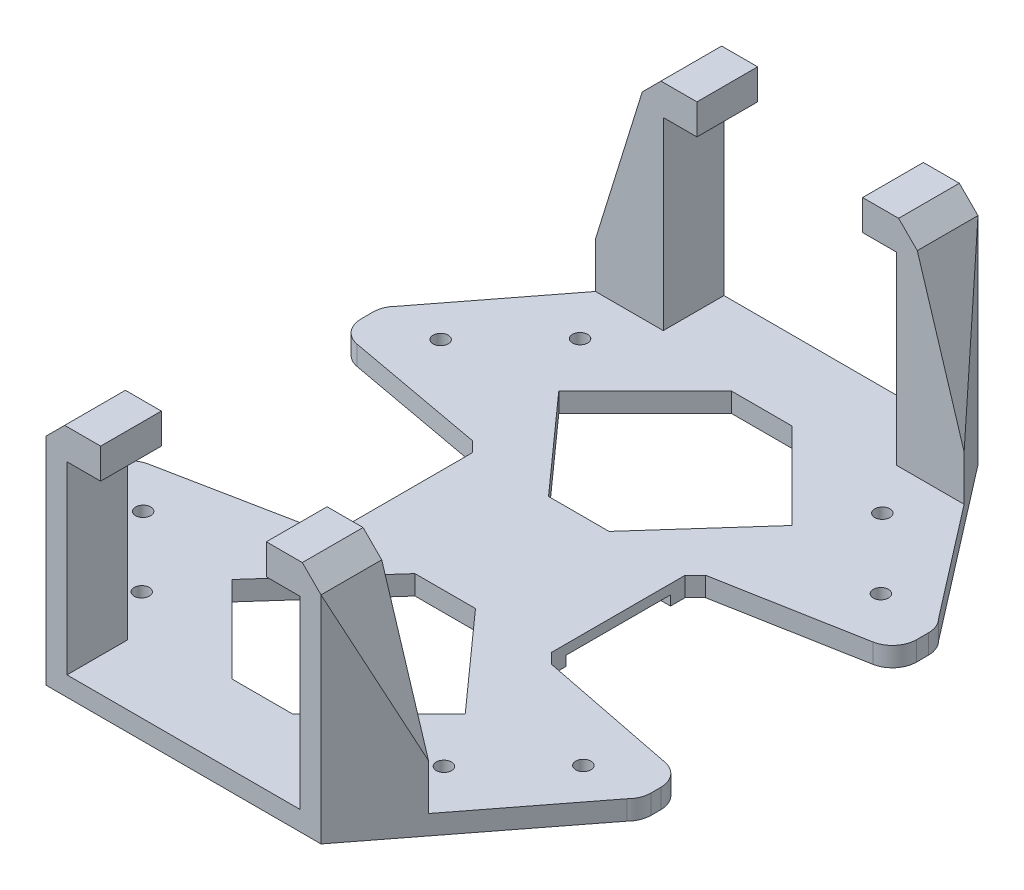
SolidWorks part; units mm, degrees
ref_plane "Front Plane" through (0, 0, 0) normal (0, 0, 1) x (1, 0, 0)
ref_plane "Top Plane" through (0, 0, 0) normal (0, 1, 0) x (1, 0, 0)
ref_plane "Right Plane" through (0, 0, 0) normal (1, 0, 0) x (0, 0, -1)
sketch "Sketch1" plane through (0, 0, 0) normal (0, 1, 0) x (1, 0, 0)
  line L0 (9.3853, 59.817) -> (7.239, 61.9633)
  line L33 (7.239, 114.554) -> (2.8509, 114.554)
  line L34 (7.239, 114.554) -> (7.239, 98.044)
  line L35 (7.239, 98.044) -> (2.8509, 98.044)
  line L36 (2.8509, 114.554) -> (2.8509, 98.044)
  line L37 (7.239, 61.9633) -> (7.239, 98.044)
  line L38 (55.9816, 98.044) -> (60.3697, 98.044)
  line L39 (60.3697, 114.554) -> (60.3697, 98.044)
  line L40 (55.9816, 114.554) -> (60.3697, 114.554)
  line L41 (55.9816, 114.554) -> (55.9816, 98.044)
  line L42 (55.9816, -22.86) -> (55.9816, -6.35)
  line L43 (55.9816, -22.86) -> (60.3697, -22.86)
  line L44 (60.3697, -22.86) -> (60.3697, -6.35)
  line L45 (55.9816, -6.35) -> (60.3697, -6.35)
  line L46 (7.239, -6.35) -> (2.8509, -6.35)
  line L47 (2.8509, -22.86) -> (2.8509, -6.35)
  line L48 (7.239, -22.86) -> (2.8509, -22.86)
  line L49 (7.239, -22.86) -> (7.239, -6.35)
  line L50 (-26.4861, 76.962) -> (2.8509, 106.299)
  line L51 (2.8509, -14.605) -> (-26.4861, 14.732)
  line L52 (-26.4861, 14.732) -> (-26.4861, 76.962)
  line L53 (7.239, 61.9633) -> (-26.4861, 68.1505)
  line L54 (7.239, 29.7307) -> (-26.4861, 23.0392)
  line L55 (60.3697, -14.605) -> (89.7067, 14.732)
  line L56 (9.3853, 31.877) -> (7.239, 29.7307)
  line L57 (9.3853, 59.817) -> (53.8353, 59.817)
  line L58 (9.3853, 59.817) -> (9.3853, 31.877)
  line L59 (9.3853, 31.877) -> (53.8353, 31.877)
  line L60 (53.8353, 59.817) -> (53.8353, 31.877)
  line L61 (7.239, 29.7307) -> (7.239, -6.35)
  line L62 (55.9816, 29.7307) -> (89.7067, 23.0392)
  line L63 (55.9816, 29.7307) -> (55.9816, -6.35)
  line L64 (53.8353, 31.877) -> (55.9816, 29.7307)
  line L65 (53.8353, 59.817) -> (55.9816, 61.9633)
  line L66 (55.9816, 61.9633) -> (55.9816, 98.044)
  line L67 (7.239, 11.6903) -> (25.2794, -6.35)
  line L68 (7.239, 114.554) -> (55.9816, 114.554)
  line L69 (7.239, 114.554) -> (7.239, 98.044)
  line L70 (7.239, 98.044) -> (55.9816, 98.044)
  line L71 (55.9816, 114.554) -> (55.9816, 98.044)
  line L72 (7.239, -6.35) -> (55.9816, -6.35)
  line L73 (7.239, -6.35) -> (7.239, -22.86)
  line L74 (7.239, -22.86) -> (55.9816, -22.86)
  line L75 (55.9816, -6.35) -> (55.9816, -22.86)
  line L76 (55.9816, 11.6903) -> (37.9412, -6.35)
  line L77 (55.9816, 61.9633) -> (89.7067, 68.1505)
  line L78 (7.239, 80.0037) -> (25.2794, 98.044)
  line L79 (55.9816, 80.0037) -> (37.9412, 98.044)
  line L80 (89.7067, 14.732) -> (89.7067, 76.962)
  line L81 (89.7067, 76.962) -> (60.3697, 106.299)
  line L82 (7.239, 80.0037) -> (25.2794, 59.817)
  line L83 (55.9816, 80.0037) -> (37.9412, 59.817)
  line L84 (7.239, 11.6903) -> (25.2794, 31.877)
  line L85 (55.9816, 11.6903) -> (37.9412, 31.877)
  line L86 (31.6103, 114.554) -> (31.6103, 103.0092)
  circle A6 centre (0, 91.694) radius 1.5875
  circle A7 centre (-14.4272, 76.962) radius 1.5875
  circle A8 centre (-14.4272, 14.732) radius 1.5875
  circle A9 centre (0, 0) radius 1.5875
  circle A10 centre (63.2206, 0) radius 1.5875
  circle A11 centre (77.6478, 14.732) radius 1.5875
  circle A12 centre (77.6478, 76.962) radius 1.5875
  circle A13 centre (63.2206, 91.694) radius 1.5875
  dimension "D5" = 44.45
  dimension "D6" = 27.94
extrude "Boss-Extrude2" add sketch "Sketch1" along normal blind 4.064 contours L53 L37 L35 L36 L50 L52 A7 A6 | L61 L54 L52 L51 L47 L46 A9 A8 | L55 L80 L62 L63 L45 L44 A11 A10 | L80 L81 L39 L38 L66 L77 A13 A12 | L34 L70 L41 L68 | L40 L41 L38 L39 | L33 L36 L35 L34 | L48 L49 L46 L47 | L49 L74 L42 L72 | L45 L42 L43 L44 | L63 L76 L72 | L85 L63 L64 L59 | L61 L84 L59 L56 | L61 L72 L67 | L60 L57 L58 L59 | L82 L37 L0 L57 | L37 L78 L70 | L79 L66 L70 | L66 L83 L57 L65 region at (13.3203, 0, -66.6229) region at (31.6103, 0, -45.847) region at (-6.2497, 0, -79.8491) region at (13.3203, 0, -25.0711) region at (13.2525, 0, -92.0306) region at (49.9003, 0, -66.6229) region at (-6.1647, 0, -11.7165) region at (5.0449, 0, -106.299) region at (7.7536, 0, -106.299) region at (69.4703, 0, -79.8491) region at (49.9681, 0, -92.0306) region at (13.2525, 0, 0.3366) region at (49.9003, 0, -25.0711) region at (58.1757, 0, -106.299) region at (5.0449, 0, 14.605) region at (31.6103, 0, 14.605) region at (69.3853, 0, -11.7165) region at (49.9681, 0, 0.3366) region at (58.1757, 0, 14.605)
sketch "Sketch3" plane through (9.3853, 0, 0) normal (-1, 0, 0) x (0, 0, 1)
  line L0 (-59.817, 0) -> (-31.877, 0) construction
  line L13 (-34.9187, 0) -> (-56.7753, 0)
  line L14 (-45.847, 0) -> (-45.847, 2.032)
  line L15 (-34.9187, 2.032) -> (-56.7753, 2.032)
  line L16 (-56.7753, 0) -> (-56.7753, 2.032)
  line L17 (-34.9187, 0) -> (-34.9187, 2.032)
extrude "Boss-Extrude3" add sketch "Sketch1<7>" along normal blind 42.672 contours L33 L36 L35 L34 | L40 L41 L38 L39 | L45 L42 L43 L44 | L48 L49 L46 L47 region at (5.0449, 0, -106.299) region at (58.1757, 0, -106.299) region at (5.0449, 0, 14.605) region at (58.1757, 0, 14.605)
sketch "Sketch1<7>" plane through (0, 0, 0) normal (0, 1, 0) x (1, 0, 0) same geometry as "Sketch1"
fillet "Fillet1" radius 5.08 1 edges at (-26.4861, 2.032, -76.962)
fillet "Fillet2" radius 5.08 1 edges at (-26.4861, 2.032, -68.1505)
fillet "Fillet3" radius 5.08 6 edges at (89.7067, 2.032, -68.1505) (89.7067, 2.032, -76.962) (89.7067, 2.032, -14.732) (89.7067, 2.032, -23.0392) (-26.4861, 2.032, -14.732) (-26.4861, 2.032, -23.0392)
extrude "Cut-Extrude1" cut sketch "Sketch3" against normal through all contours L15 L16 L13 L17
sketch "Sketch4" plane through (0, 0, 0) normal (0, -1, 0) x (1, 0, 0)
  line L0 (60.3697, -114.554) -> (88.2188, -78.4499)
  line L1 (88.2188, -78.4499) -> (60.3697, -106.299)
  line L2 (60.3697, -106.299) -> (60.3697, -114.554)
  line L3 (9.3853, -45.847) -> (28.8242, -45.847)
  line L4 (9.3853, -34.9187) -> (9.3853, -56.7753) construction
  line L5 (31.6103, -34.9187) -> (31.6103, -47.4802)
  line L6 (9.3853, -34.9187) -> (53.8353, -34.9187) construction
  line L7 (-24.9982, -78.4499) -> (2.8509, -106.299)
  line L8 (2.8509, -114.554) -> (-24.9982, -78.4499)
  line L9 (2.8509, -106.299) -> (2.8509, -114.554)
  line L10 (2.8509, 22.86) -> (-24.9982, -13.2441)
  line L11 (2.8509, 14.605) -> (2.8509, 22.86)
  line L12 (-24.9982, -13.2441) -> (2.8509, 14.605)
  line L13 (88.2188, -13.2441) -> (60.3697, 14.605)
  line L14 (60.3697, 22.86) -> (88.2188, -13.2441)
  line L15 (60.3697, 14.605) -> (60.3697, 22.86)
  line M18 (-24.9982, -78.4499) -> (2.8509, -106.299)
  line M19 (2.8509, -106.299) -> (2.8509, -114.554)
  line M21 (60.3697, -114.554) -> (60.3697, -106.299)
  line M22 (60.3697, -106.299) -> (88.2188, -78.4499)
extrude "Boss-Extrude4" add sketch "Sketch4" against normal up to surface (4.064 mm away) contours L8 M19 M18 | L0 M21 M22 | L15 L13 L14 | L10 L12 L11 region at (69.6528, 0, -99.7676) region at (-6.4322, 0, -99.7676) region at (-6.4322, 0, 8.0736) region at (69.6528, 0, 8.0736) up to face at (31.6103, 4.064, -12.4058)
sketch "Sketch6" plane through (0, 42.672, 0) normal (0, 1, 0) x (1, 0, 0)
  line L0 (60.3697, 114.554) -> (60.3697, 101.854)
  line L1 (60.3697, 114.554) -> (60.3697, 98.044) construction
  line L2 (2.8509, -22.86) -> (2.8509, -6.35) construction
  line L3 (60.3697, 101.854) -> (2.8509, 101.854)
  line L4 (60.3697, 101.854) -> (60.3697, -10.16)
  line L5 (60.3697, -10.16) -> (2.8509, -10.16)
  line L6 (2.8509, 101.854) -> (2.8509, -10.16)
  line L7 (55.9816, -22.86) -> (7.239, -22.86) construction
  line M4 (55.9816, 114.554) -> (55.9816, 98.044)
  line M5 (55.9816, 98.044) -> (60.3697, 98.044)
  line M6 (60.3697, 98.044) -> (60.3697, 114.554)
  dimension "D1" = 12.7
  dimension "D2" = 12.7
extrude "Cut-Extrude2" cut sketch "Sketch6" along direction (0, 1, 0) on the side against the normal up to surface (38.608 mm away) contours L3 L6 L5 L4 M5 M4 | L3 M6 M4 M5 region at (58.1757, 42.672, -99.949) region at (31.5412, 42.672, -45.7062) up to face at (31.6103, 4.064, -12.4058)
ref_plane "Plane2" through (0, 0, -45.847) normal (0, 0, 1) x (1, 0, 0)
sketch "Sketch7" plane through (0, 0, 22.86) normal (0, 0, 1) x (1, 0, 0)
  line L1 (60.3697, 42.672) -> (48.9397, 42.672)
  line L2 (60.3697, 42.672) -> (60.3697, 49.022)
  line L3 (60.3697, 49.022) -> (48.9397, 49.022)
  line L4 (48.9397, 42.672) -> (48.9397, 49.022)
  line L5 (2.8509, 42.672) -> (14.2809, 42.672)
  line L6 (2.8509, 42.672) -> (2.8509, 49.022)
  line L7 (2.8509, 49.022) -> (14.2809, 49.022)
  line L8 (14.2809, 42.672) -> (14.2809, 49.022)
  dimension "D1" = 11.43
  dimension "D2" = 11.43
  dimension "D3" = 6.35
  dimension "D4" = 6.35
extrude "Boss-Extrude5" add sketch "Sketch7" against normal up to surface (12.7 mm away) up to face at (58.1757, 23.368, 10.16)
chamfer "Chamfer2" distance 3.904 angle 45 2 edges at (2.8509, 49.022, 16.51) (60.3697, 49.022, 16.51)
sketch "Sketch8" plane through (0, 0, -114.554) normal (0, 0, -1) x (-1, 0, 0)
  line L1 (-60.3697, 42.672) -> (-48.9397, 42.672)
  line L2 (-60.3697, 42.672) -> (-60.3697, 49.022)
  line L3 (-60.3697, 49.022) -> (-48.9397, 49.022)
  line L4 (-48.9397, 42.672) -> (-48.9397, 49.022)
  line L5 (-2.8509, 42.672) -> (-14.2809, 42.672)
  line L6 (-2.8509, 42.672) -> (-2.8509, 49.022)
  line L7 (-2.8509, 49.022) -> (-14.2809, 49.022)
  line L8 (-14.2809, 42.672) -> (-14.2809, 49.022)
extrude "Boss-Extrude6" add sketch "Sketch8" against normal up to surface (12.7 mm away) up to face at (5.0449, 23.368, -101.854)
chamfer "Chamfer3" distance 3.904 angle 45 2 edges at (60.3697, 49.022, -108.204) (2.8509, 49.022, -108.204)
sketch "Sketch13" plane through (0, 4.064, 0) normal (0, 1, 0) x (1, 0, 0)
  line L0 (2.8509, -10.16) -> (-6.9453, -10.16)
  line L1 (2.8509, -22.86) -> (-24.9982, 13.2441) construction
  line L2 (-6.9453, -10.16) -> (2.8509, -22.86)
  line L3 (2.8509, -22.86) -> (2.8509, -10.16)
  line L4 (60.3697, -10.16) -> (70.1659, -10.16)
  line L5 (60.3697, -22.86) -> (88.2188, 13.2441) construction
  line L6 (70.1659, -10.16) -> (60.3697, -22.86)
  line L7 (60.3697, -22.86) -> (60.3697, -10.16)
  line L8 (60.3697, 101.854) -> (70.1659, 101.854)
  line L9 (60.3697, 114.554) -> (88.2188, 78.4499) construction
  line L10 (70.1659, 101.854) -> (60.3697, 114.554)
  line L11 (60.3697, 114.554) -> (60.3697, 101.854)
  line L12 (2.8509, 114.554) -> (2.8509, 101.854)
  line L13 (2.8509, 101.854) -> (-6.9453, 101.854)
  line L14 (2.8509, 114.554) -> (-24.9982, 78.4499) construction
  line L15 (-6.9453, 101.854) -> (2.8509, 114.554)
extrude "Boss-Extrude8" add sketch "Sketch13" along normal up to vertex (41.054 mm away) up to point (60.3697, 45.118, 10.16)
sketch "Sketch14" plane through (0, 0, -101.854) normal (0, 0, 1) x (1, 0, 0)
  line L0 (60.3697, 45.118) -> (70.1659, 13.562)
  line L1 (70.1659, 45.118) -> (70.1659, 4.064) construction
  line L2 (60.3697, 45.118) -> (70.1659, 45.118)
  line L3 (60.3697, 45.118) -> (70.1659, 45.118)
  line L4 (31.6103, 4.064) -> (31.6103, 15.6899)
  line L5 (25.2794, 4.064) -> (37.9412, 4.064) construction
  line L6 (70.1659, 13.562) -> (70.1659, 45.118)
  line L7 (-6.9453, 13.562) -> (-6.9453, 45.118)
  line L8 (2.8509, 45.118) -> (-6.9453, 13.562)
  line L9 (2.8509, 45.118) -> (-6.9453, 45.118)
  line L10 (-6.9453, 45.118) -> (-6.9453, 13.562)
  line L11 (60.3697, 45.118) -> (70.1659, 13.562)
  line L12 (70.1659, 45.118) -> (70.1659, 13.562)
  line L13 (60.3697, 45.118) -> (70.1659, 45.118)
  line L14 (70.1659, 13.562) -> (70.1659, 45.118)
  line M6 (70.1659, 4.064) -> (70.1659, 45.118)
  line M7 (70.1659, 45.118) -> (60.3697, 45.118)
extrude "Cut-Extrude7" cut sketch "Sketch14" against normal blind 26.67 contours L8 L9 L7 | L0 M7 M6 region at (66.9005, 34.5993, -101.854) region at (-3.6799, 34.5993, -101.854)
sketch "Sketch17" plane through (0, 0, 10.16) normal (0, 0, -1) x (-1, 0, 0)
  line L0 (-70.1659, 45.118) -> (-70.1659, 13.622)
  line L1 (-70.1659, 45.118) -> (-70.1659, 4.064) construction
  line L2 (-70.1659, 13.622) -> (-60.3697, 45.118)
  line L3 (-60.3697, 45.118) -> (-70.1659, 45.118)
  line L4 (6.9453, 45.118) -> (6.9453, 13.622)
  line L5 (6.9453, 45.118) -> (6.9453, 4.064) construction
  line L6 (6.9453, 13.622) -> (-2.8509, 45.118)
  line L7 (-2.8509, 45.118) -> (6.9453, 45.118)
  dimension "D1" = 31.496
  dimension "D2" = 31.496
extrude "Cut-Extrude8" cut sketch "Sketch17" against normal blind 26.67
